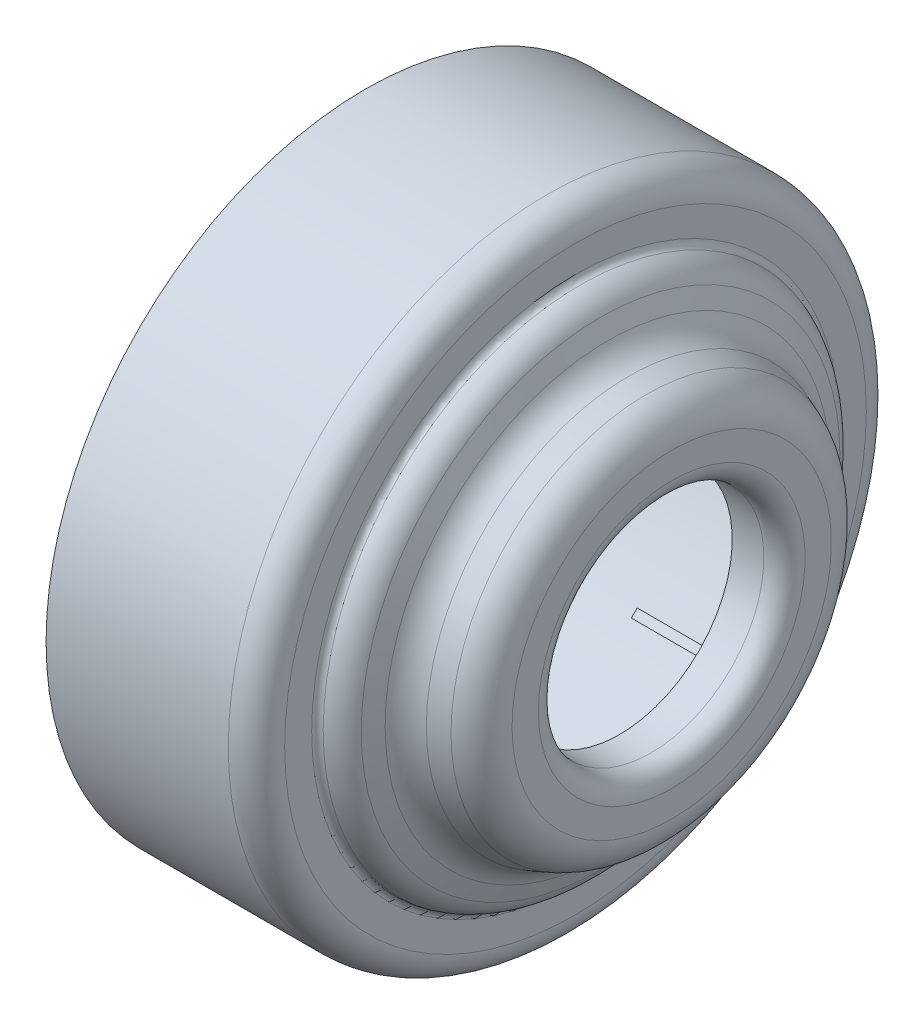
SolidWorks part; units mm, degrees
ref_plane "前视基准面" through (0, 0, 0) normal (0, 0, 1) x (1, 0, 0)
ref_plane "上视基准面" through (0, 0, 0) normal (0, 1, 0) x (1, 0, 0)
ref_plane "右视基准面" through (0, 0, 0) normal (1, 0, 0) x (0, 0, -1)
sketch "草图1" plane through (0, 0, 0) normal (0, 0, 1) x (1, 0, 0)
  line L0 (-28.9725, 0) -> (27.6414, 0) construction
  line L1 (0, 33.7643) -> (0, -38.2898) construction
  line L9 (-14.5, 22) -> (-1.25, 22)
  line L10 (-0.4, 21.15) -> (-0.4, 18.1)
  line L11 (0.1, 17.6) -> (0.5109, 17.6)
  line L12 (1.522, 16.9333) -> (2.0436, 15.7161)
  line L13 (4.2589, 13.6007) -> (5.5618, 13.1121)
  line L14 (6.6, 11.614) -> (6.6, 9.9)
  line L15 (6.1, 9.4) -> (4, 9.4)
  line L17 (4, 9.4) -> (4, 8.2)
  line L18 (-14.5, 23.2) -> (-1.25, 23.2)
  line L19 (-0.4, 23.7801) -> (-0.4, -6.5039) construction
  line L20 (0.8, 21.15) -> (0.8, 19.1865)
  line L21 (-14.5, 23.2) -> (-14.5, 22)
  line L22 (2.6249, 17.406) -> (3.1466, 16.1888)
  line L23 (4.6803, 14.7243) -> (5.9831, 14.2357)
  line L24 (7.8, 11.614) -> (7.8, 9.7)
  line L25 (6.3, 8.2) -> (4, 8.2)
  line L26 (6.6, 11.614) -> (6.6, 10.5328) construction
  line L27 (0.8, 21.15) -> (0.8, 18.7818) construction
  line L28 (0.8, 18.7818) -> (0.8, 18.7818) construction
  line L29 (4, 9.4) -> (4, 9) construction
  line L30 (5.5608, 8.2) -> (4.8944, 8.2) construction
  line L31 (5.6477, 9.4) -> (4, 9.4) construction
  line L32 (4.8944, 8.2) -> (4.8944, 8.2) construction
  line L33 (7.8, 11.614) -> (7.8, 10.7015) construction
  arc A6 (-0.4, 21.15) -> (-1.25, 22) centre (-1.25, 21.15) ccw
  arc A8 (1.522, 16.9333) -> (0.5109, 17.6) centre (0.5109, 16.5) ccw
  arc A9 (2.0436, 15.7161) -> (4.2589, 13.6007) centre (5.6283, 17.2524) ccw
  arc A10 (6.6, 11.614) -> (5.5618, 13.1121) centre (5, 11.614) ccw
  arc A12 (0.1, 17.6) -> (-0.4, 18.1) centre (0.1, 18.1) cw
  arc A13 (0.8, 21.15) -> (-1.25, 23.2) centre (-1.25, 21.15) ccw
  arc A14 (7.8, 10.7015) -> (5.5608, 8.2) centre (5.8037, 10.2356) cw construction
  arc A15 (2.6249, 17.406) -> (1.1591, 18.7068) centre (0.5109, 16.5) ccw
  arc A16 (3.1466, 16.1888) -> (4.6803, 14.7243) centre (5.6283, 17.2524) ccw
  arc A17 (7.8, 11.614) -> (5.9831, 14.2357) centre (5, 11.614) ccw
  arc A19 (2.6249, 17.406) -> (0.8, 18.7818) centre (0.5109, 16.5) ccw construction
  arc A20 (0.8, 19.1865) -> (1.1591, 18.7068) centre (1.3, 19.1865) ccw
  arc A21 (0.8, 18.7818) -> (0.8, 18.7818) centre (0.8, 18.7818) cw construction
  arc A22 (6.6, 10.5328) -> (5.6477, 9.4) centre (5.8037, 10.2356) cw construction
  arc A23 (6.6, 9.9) -> (6.1, 9.4) centre (6.1, 9.9) cw
  arc A24 (7.8, 9.7) -> (6.3, 8.2) centre (6.3, 9.7) cw
  point P15 (0, 22.4)
  point P24 (3, 14.5)
  point P27 (7, 13)
  point P30 (7, 9)
  dimension "D11" = 0.85
  dimension "D12" = 0.4
  dimension "D13" = 0.5
  dimension "D14" = 2.6
  dimension "D15" = 1.5
  dimension "D5" = 0.5
  dimension "D8" = 0.5
  dimension "D2" = 18.8
  dimension "D3" = 35.2
  dimension "D4" = 29
  dimension "D6" = 1.2
  dimension "D7" = 3
  dimension "D9" = 26
  dimension "D10" = 4
  dimension "D18" = 44
revolve "旋转1" add sketch "草图1" angle 360 about L0
ref_plane "基准面2" through (-7.3, 0, 0) normal (-1, 0, 0) x (0, 0, 1)
sketch "草图4" plane through (-7.3, 0, 0) normal (-1, 0, 0) x (0, 0, 1)
  line L0 (-33.0285, 0) -> (34.8844, 0) construction
  line L1 (0, 28.0106) -> (0, -28.3543) construction
  line L2 (-0.3, 21.998) -> (-0.3, 17.5)
  line L3 (-0.3, 17.5) -> (0.3, 17.5)
  line L4 (0.3, 21.998) -> (0.3, 17.5)
  circle A0 centre (0, 0) radius 22 construction
  arc A1 (0.3, 21.998) -> (-0.3, 21.998) centre (0, 0) ccw
  point P9 (0, 17.5)
  dimension "D1" = 0.6
  dimension "D2" = 17.5
extrude "凸台-拉伸1" add sketch "草图4" against normal up to surface (6.9 mm away) contours L2 L3 L4 A1 up to face at (-0.4, 0, 18.1)
fillet "圆角1" radius 1 1 edges at (-0.4, 17.5, 0)
pattern_circular "阵列(圆周)1" count 8 over 360 about axis through (-14.5, 0, 0) along (-1, 0, 0) of "凸台-拉伸1", "圆角1"
